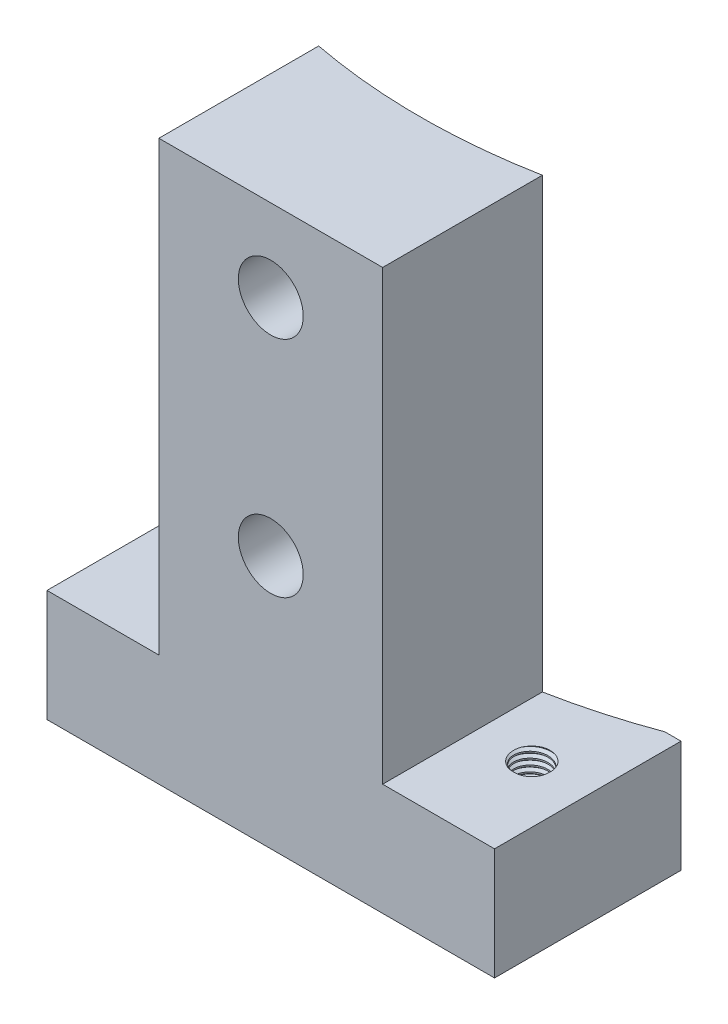
SolidWorks part; units mm, degrees
ref_plane "Ebene vorne" through (0, 0, 0) normal (0, 0, 1) x (1, 0, 0)
ref_plane "Ebene oben" through (0, 0, 0) normal (0, 1, 0) x (1, 0, 0)
ref_plane "Ebene rechts" through (0, 0, 0) normal (1, 0, 0) x (0, 0, -1)
sketch "Skizze1" plane through (0, 0, 0) normal (0, 0, 1) x (1, 0, 0)
  line L1 (-15, 37.5) -> (15, 37.5)
  line L2 (-15, 37.5) -> (-15, -37.5)
  line L3 (-15, -37.5) -> (15, -37.5)
  line L4 (15, 37.5) -> (15, -37.5)
  line L5 (-15, 37.5) -> (15, -37.5) construction
  line L6 (-15, -37.5) -> (15, 37.5) construction
  point P0 (0, 0)
  dimension "D1" = 75
  dimension "D2" = 30
extrude "Aufsatz-Linear austragen1" add sketch "Skizze1" along normal blind 25
sketch "Skizze2" plane through (0, -37.5, 0) normal (0, -1, 0) x (1, 0, 0)
  line L0 (-15, 25) -> (15, 25) construction
  line L1 (-30, 0) -> (30, 0)
  line L2 (-30, 0) -> (-30, 25)
  line L3 (-30, 25) -> (30, 25)
  line L4 (30, 0) -> (30, 25)
  line L5 (-15, 0) -> (15, 0) construction
  line L6 (-15, 25) -> (-15, 0) construction
  line L7 (15, 25) -> (15, 0) construction
  dimension "D1" = 0
  dimension "D2" = 0
  dimension "D3" = 15
  dimension "D4" = 15
extrude "Aufsatz-Linear austragen2" add sketch "Skizze2" against normal blind 15
sketch "Skizze3" plane through (0, 37.5, 0) normal (0, 1, 0) x (1, 0, 0)
  circle A0 centre (0, 75) radius 80
  dimension "D1" = 160
  dimension "D2" = 75
extrude "Schnitt-Linear austragen1" cut sketch "Skizze3" against normal blind 80
sketch "Skizze4" plane through (0, 0, 25) normal (0, 0, 1) x (1, 0, 0)
  line L0 (-30, -37.5) -> (30, -37.5) construction
  circle A0 centre (0, -3.5) radius 2.6
  circle A1 centre (0, 26.5) radius 2.6
  dimension "D3" = 5.2
  dimension "D4" = 5.2
  dimension "D1" = 64
  dimension "D2" = 30
extrude "Schnitt-Linear austragen2" cut sketch "Skizze4" against normal blind 80
sketch "Skizze5" plane through (0, 0, 25) normal (0, 0, 1) x (1, 0, 0)
  circle A0 centre (0, -3.5) radius 4.35
  circle A1 centre (0, 26.5) radius 4.35
  dimension "D1" = 8.7
  dimension "D2" = 8.7
extrude "Schnitt-Linear austragen3" cut sketch "Skizze5" against normal blind 13
sketch "Skizze6" plane through (0, -22.5, 0) normal (0, 1, 0) x (1, 0, 0)
  line L0 (30, 0) -> (30, -25) construction
  line L1 (-30, -25) -> (-30, 0) construction
  line L2 (-15, -25) -> (-30, -25) construction
  line L3 (30, -25) -> (15, -25) construction
  circle A0 centre (-22.5, -12.5) radius 2.3
  circle A1 centre (22.5, -12.5) radius 2.3
  dimension "D1" = 4.6
  dimension "D2" = 4.6
  dimension "D3" = 7.5
  dimension "D4" = 7.5
  dimension "D5" = 12.5
  dimension "D6" = 12.5
extrude "Schnitt-Linear austragen4" cut sketch "Skizze6" against normal blind 18
thread "Gewinde1" pitch 0.8 start angle 0, offset 0, length 20, pitch 0.8, diameter 4.6
ref_plane "Ebene1" through (24.8, -37.5, 12.5) normal (0, 0, 1) x (1, 0, 0)
sketch "Gewindeprofil1" plane through (24.8, -37.5, 12.5) normal (0, 0, 1) x (1, 0, 0)
  line L0 (0, 0) -> (0, 0.8) construction
  line L1 (0, 0) -> (0.433, 0.25)
  line L2 (0.433, 0.25) -> (0.433, 0.35)
  line L3 (0.433, 0.35) -> (0, 0.6)
  line L4 (0.433, 0.3) -> (0, 0.3) construction
  line L11 (0, 0) -> (0, 0.6)
  point P2 (0, 0)
  dimension "Pitch" = 0.8
  dimension "Profile_Angle" = 60
  dimension "Profile_Land" = 0.1
  dimension "Profile_Height" = 0.433
thread "Gewinde2" pitch 0.8 profile "Gewindeprofil2" start angle 0, offset 0, length 20, pitch 0.8, diameter 4.6
ref_plane "Ebene2" through (-20.2, -37.5, 12.5) normal (0, 0, 1) x (1, 0, 0)
sketch "Gewindeprofil2" plane through (-20.2, -37.5, 12.5) normal (0, 0, 1) x (1, 0, 0)
  line L0 (0, 0) -> (0, 0.8) construction
  line L1 (0, 0) -> (0.433, 0.25)
  line L2 (0.433, 0.25) -> (0.433, 0.35)
  line L3 (0.433, 0.35) -> (0, 0.6)
  line L4 (0.433, 0.3) -> (0, 0.3) construction
  line L11 (0, 0) -> (0, 0.6)
  point P2 (0, 0)
  dimension "Pitch" = 0.8
  dimension "Profile_Angle" = 60
  dimension "Profile_Land" = 0.1
  dimension "Profile_Height" = 0.433
